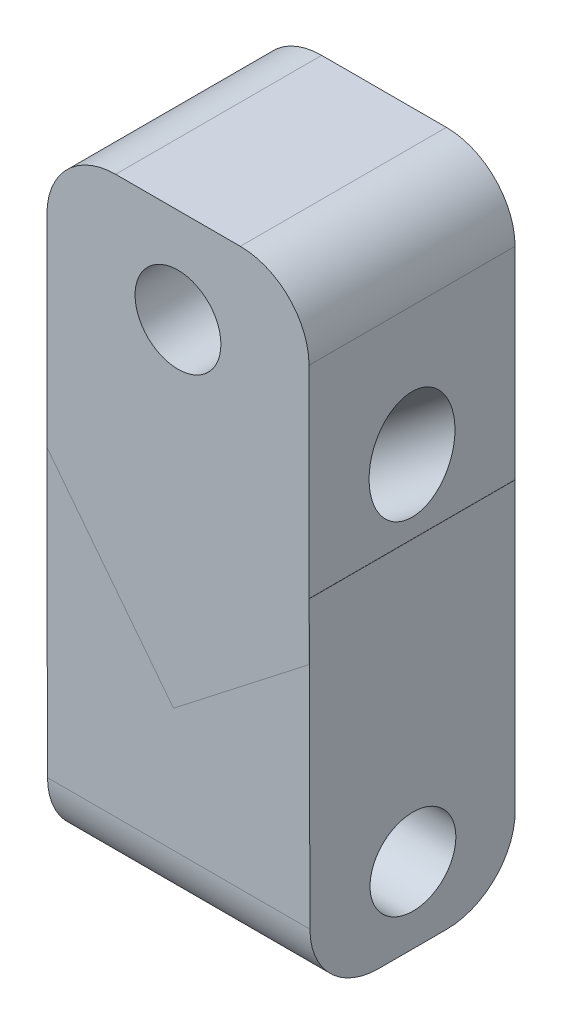
SolidWorks part; units mm, degrees
ref_plane "Front Plane" through (0, 0, 0) normal (0, 0, 1) x (1, 0, 0)
ref_plane "Top Plane" through (0, 0, 0) normal (0, 1, 0) x (1, 0, 0)
ref_plane "Right Plane" through (0, 0, 0) normal (1, 0, 0) x (0, 0, -1)
sketch "Sketch3" plane through (0, 0, 0) normal (0, 0, 1) x (1, 0, 0)
  line L3 (0, 0) -> (58.4671, 45.5154)
  line L4 (58.4671, 45.5154) -> (58.4671, 0)
  line L5 (58.4671, 0) -> (0, 0)
  point P0 (0, 0)
  dimension "D1" = 37.9
ref_plane "Plane1" through (0, 0, 0) normal (0.7891, 0.6143, 0) x (0, 0, -1)
sketch "Sketch5" plane through (0, 0, 0) normal (0.7891, 0.6143, 0) x (0, 0, -1)
  line L1 (-30, -30) -> (30, -30)
  line L2 (-30, -30) -> (-30, 30)
  line L3 (-30, 30) -> (30, 30)
  line L4 (30, -30) -> (30, 30)
  line L5 (-30, -30) -> (30, 30) construction
  line L6 (-30, 30) -> (30, -30) construction
  circle A0 centre (0, 0) radius 12.5
  point P0 (0, 0)
  dimension "D3" = 25
  dimension "D1" = 60
  dimension "D2" = 60
extrude "Boss-Extrude3" add sketch "Sketch5" along normal mid plane 50
sketch "Sketch9" plane through (0, 0, 0) normal (0, 0, 1) x (1, 0, 0)
  line L0 (38.1557, -8.3154) -> (38.1557, 67.1791)
  line L1 (18.1557, 87.1791) -> (-18.1557, 87.1791)
  line L2 (-38.1557, 67.1791) -> (-38.1557, 8.3154)
  line L3 (-38.1557, 8.3154) -> (38.1557, -8.3154)
  circle A0 centre (0, 59.5973) radius 12.5
  arc A1 (18.1557, 87.1791) -> (38.1557, 67.1791) centre (18.1557, 67.1791) cw
  arc A2 (-18.1557, 87.1791) -> (-38.1557, 67.1791) centre (-18.1557, 67.1791) ccw
  dimension "D1" = 25
  dimension "D2" = 20
extrude "Boss-Extrude5" add sketch "Sketch9" along normal mid plane 60
sketch "Sketch10" plane through (0, 0, 0) normal (1, 0, 0) x (0, 0, -1)
  line L1 (-9.7825, -95.0636) -> (10, -95.0636)
  line L4 (30, 8.3154) -> (30, -75.0636)
  line L5 (-30, 8.3154) -> (-29.7825, -75.1157)
  line L6 (-30, 8.3154) -> (30, 8.3154)
  circle A0 centre (0.2123, -73.0636) radius 12.5
  arc A1 (30, -75.0636) -> (10, -95.0636) centre (10, -75.0636) cw
  arc A2 (-29.7825, -75.1157) -> (-9.7825, -95.0636) centre (-9.7825, -75.0636) ccw
  dimension "D1" = 25
  dimension "D2" = 30
  dimension "D3" = 22
  dimension "D4" = 20
extrude "Boss-Extrude6" add sketch "Sketch10" along normal mid plane 76.42
extrude "Cut-Extrude2" cut sketch "Sketch5<2>" against normal mid plane 230 contours A0
sketch "Sketch5<2>" plane through (0, 0, 0) normal (0.7891, 0.6143, 0) x (0, 0, -1) same geometry as "Sketch5"
